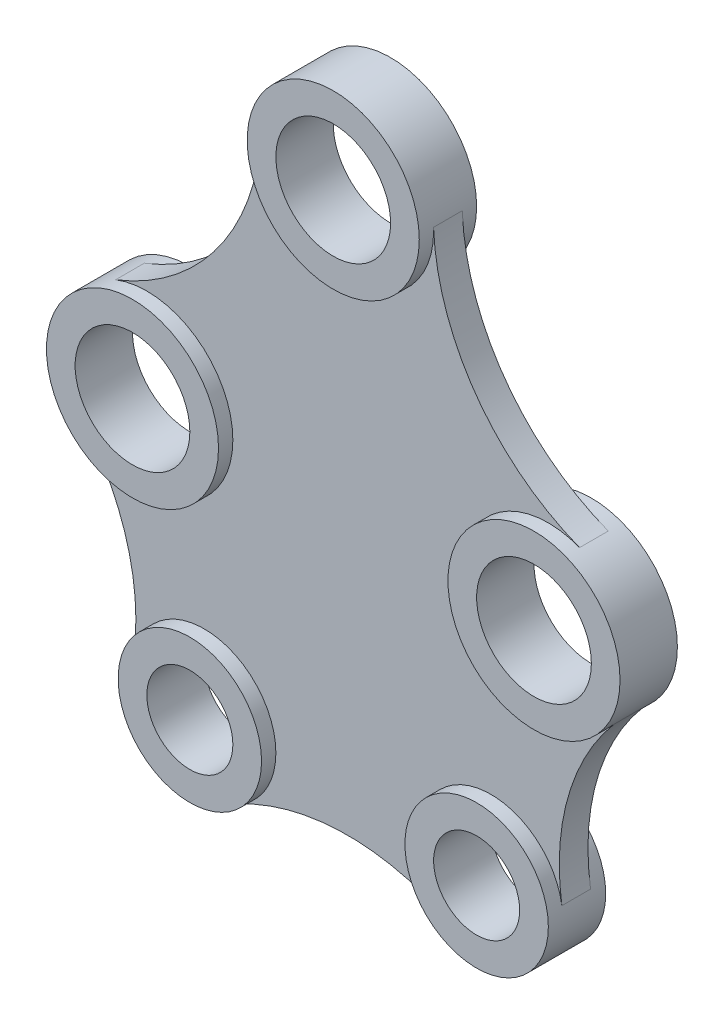
SolidWorks part; units mm, degrees
ref_plane "Front Plane" through (0, 0, 0) normal (0, 0, 1) x (1, 0, 0)
ref_plane "Top Plane" through (0, 0, 0) normal (0, 1, 0) x (1, 0, 0)
ref_plane "Right Plane" through (0, 0, 0) normal (1, 0, 0) x (0, 0, -1)
sketch "Sketch1" plane through (0, 0, 0) normal (0, 0, 1) x (1, 0, 0)
  line L0 (0, 0) -> (0, 50000) construction
  circle A0 centre (70, 0) radius 20
  circle A1 centre (70, 0) radius 30
  circle A2 centre (50, -87) radius 25
  circle A3 centre (50, -87) radius 15
  circle A4 centre (0, 98) radius 30
  circle A5 centre (0, 98) radius 20
  arc A6 (29.9748, 99.2288) -> (80.8839, 27.956) centre (109.9077, 102.5055) ccw
  arc A7 (92.8576, -19.4302) -> (74.7169, -83.2486) centre (153.8111, -71.2439) ccw
  circle A8 centre (-50, -87) radius 15
  circle A9 centre (-50, -87) radius 25
  arc A10 (-92.8576, -19.4302) -> (-74.7169, -83.2486) centre (-153.8111, -71.2439) cw
  arc A11 (-29.9748, 99.2288) -> (-80.8839, 27.956) centre (-109.9077, 102.5055) cw
  circle A12 centre (-70, 0) radius 20
  circle A13 centre (-70, 0) radius 30
  arc A14 (-38.0952, -108.9836) -> (38.0952, -108.9836) centre (0, -179.3309) cw
  dimension "D1" = 40
  dimension "D2" = 60
  dimension "D3" = 50
  dimension "D4" = 30
  dimension "D5" = 60
  dimension "D6" = 40
  dimension "D7" = 80
  dimension "D8" = 80
  dimension "D13" = 80
  dimension "D9" = 185
  dimension "D10" = 50
  dimension "D11" = 98
  dimension "D12" = 140
extrude "Boss-Extrude1" add sketch "Sketch1" along normal mid plane 10 contours A14 L0 A4 A11 A13 A10 A9 | L0 A14 A2 A7 A1 A6 A4 region at (0, -11.3856, 0)
extrude "Boss-Extrude2" add sketch "Sketch1<3>" along normal mid plane 20 contours A4 L0 A5 | L0 A4 A5 | A1 A0 | A13 A12 | A9 A8 | A2 A3 region at (-21.1593, 77.6903, 0) region at (0.6708, 73, 0) region at (-53.5455, 24.0636, 0) region at (94.0636, 16.4545, 0) region at (-48.1721, -62.776, 0) region at (74.224, -85.1721, 0)
sketch "Sketch1<3>" plane through (0, 0, 0) normal (0, 0, 1) x (1, 0, 0) same geometry as "Sketch1"
